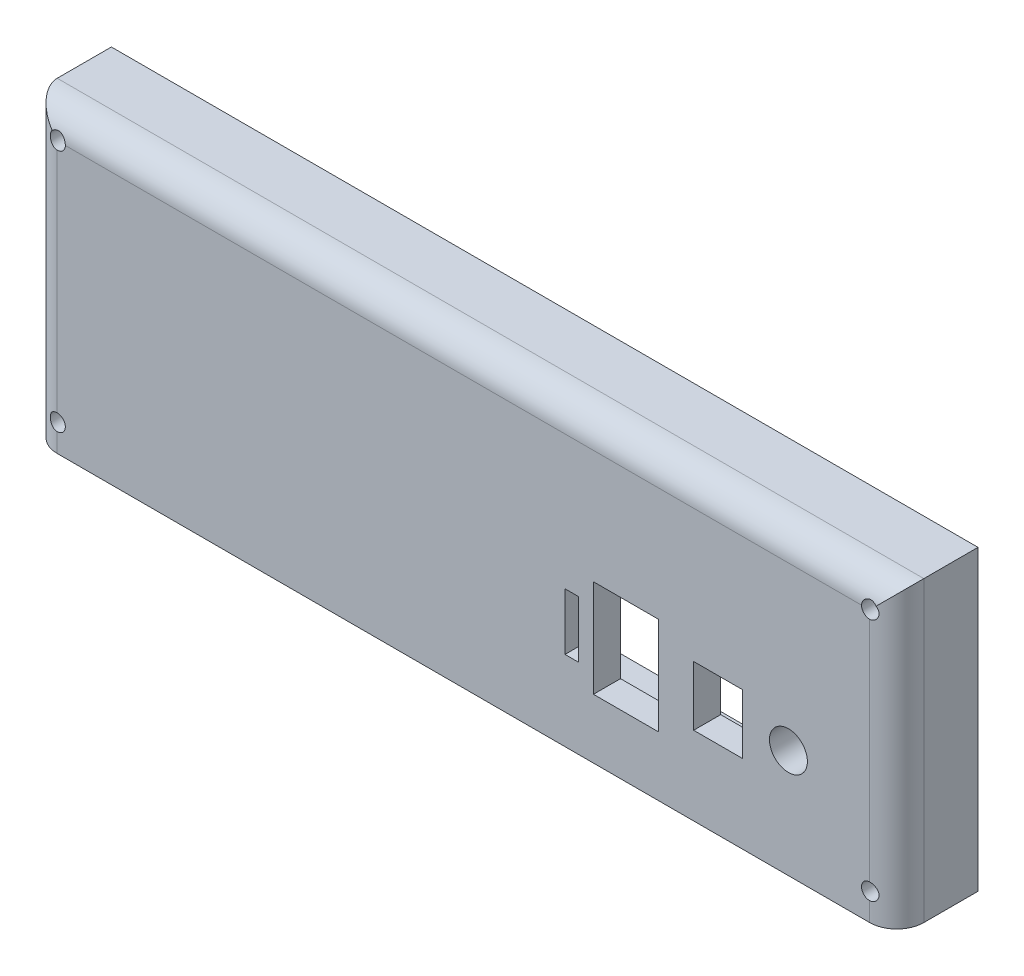
SolidWorks part; units mm, degrees
ref_plane "Спереди" through (0, 0, 0) normal (0, 0, 1) x (1, 0, 0)
ref_plane "Сверху" through (0, 0, 0) normal (0, 1, 0) x (1, 0, 0)
ref_plane "Справа" through (0, 0, 0) normal (1, 0, 0) x (0, 0, -1)
sketch "Эскиз1" plane through (0, 0, 0) normal (0, 0, 1) x (1, 0, 0)
  line L1 (-80, -27.5) -> (80, -27.5)
  line L2 (-80, -27.5) -> (-80, 27.5)
  line L3 (-80, 27.5) -> (80, 27.5)
  line L4 (80, -27.5) -> (80, 27.5)
  line L5 (-80, -27.5) -> (80, 27.5) construction
  line L6 (-80, 27.5) -> (80, -27.5) construction
  point P0 (0, 0)
  dimension "D1" = 55
  dimension "D2" = 160
extrude "Бобышка-Вытянуть1" add sketch "Эскиз1" along normal blind 5 contours L3 L4 L1 L2
sketch "Эскиз2" plane through (0, 0, 5) normal (0, 0, 1) x (1, 0, 0)
  line L0 (-80, -27.5) -> (80, -27.5) construction
  line L1 (42.5, -2) -> (51.5, -2)
  line L2 (42.5, -2) -> (42.5, -13)
  line L3 (42.5, -13) -> (51.5, -13)
  line L4 (51.5, -2) -> (51.5, -13)
  line L5 (42.5, -2) -> (51.5, -13) construction
  line L6 (42.5, -13) -> (51.5, -2) construction
  line L7 (80, -27.5) -> (80, 27.5) construction
  line L9 (24, 1.5) -> (36, 1.5)
  line L10 (24, 1.5) -> (24, -16.5)
  line L11 (24, -16.5) -> (36, -16.5)
  line L12 (36, 1.5) -> (36, -16.5)
  line L13 (24, 1.5) -> (36, -16.5) construction
  line L14 (24, -16.5) -> (36, 1.5) construction
  line L15 (18.75, -2.25) -> (21.25, -2.25)
  line L16 (18.75, -2.25) -> (18.75, -12.75)
  line L17 (18.75, -12.75) -> (21.25, -12.75)
  line L18 (21.25, -2.25) -> (21.25, -12.75)
  line L19 (18.75, -2.25) -> (21.25, -12.75) construction
  line L20 (18.75, -12.75) -> (21.25, -2.25) construction
  circle A0 centre (60, -7.5) radius 3.5
  point P2 (47, -7.5)
  point P12 (30, -7.5)
  point P17 (20, -7.5)
  dimension "D1" = 7
  dimension "D2" = 9
  dimension "D3" = 11
  dimension "D4" = 20
  dimension "D5" = 20
  dimension "D6" = 20
  dimension "D7" = 33
  dimension "D8" = 18
  dimension "D9" = 12
  dimension "D10" = 50
  dimension "D11" = 20
  dimension "D12" = 2.5
  dimension "D13" = 10.5
  dimension "D14" = 60
  dimension "20" = 20
extrude "Вырез-Вытянуть1" cut sketch "Эскиз2" against normal blind 5
sketch "Эскиз3" plane through (0, 0, 5) normal (0, 0, 1) x (1, 0, 0)
  line L0 (-80, -27.5) -> (-80, 27.5) construction
  line L1 (-80, 27.5) -> (80, 27.5) construction
  line L2 (-80, -27.5) -> (80, -27.5) construction
  line L3 (80, -27.5) -> (80, 27.5) construction
  circle A0 centre (-75, 22.5) radius 1.5
  circle A1 centre (-75, -22.5) radius 1.5
  circle A2 centre (75, 22.5) radius 1.5
  circle A3 centre (75, -22.5) radius 1.5
  dimension "D1" = 3
  dimension "D5" = 3
  dimension "D9" = 3
  dimension "D10" = 3
  dimension "D11" = 5
  dimension "D2" = 5
  dimension "D3" = 5
  dimension "D4" = 5
  dimension "D6" = 5
  dimension "D7" = 5
  dimension "D8" = 5
  dimension "D12" = 5
extrude "Вырез-Вытянуть2" cut sketch "Эскиз3" against normal blind 10
fillet "Скругление1" radius 5 3 edges at (-80, 0, 5) (80, 0, 5) (0, 27.5, 5)
sketch "Эскиз5" plane through (0, 0, 0) normal (0, 0, -1) x (-1, 0, 0)
  line L1 (-80, -27.5) -> (80, -27.5)
  line L2 (-80, -27.5) -> (-80, 27.5)
  line L3 (-80, 27.5) -> (80, 27.5)
  line L4 (80, -27.5) -> (80, 27.5)
  line L5 (-80, -27.5) -> (80, 27.5) construction
  line L6 (-80, 27.5) -> (80, -27.5) construction
  point P0 (0, 0)
extrude "Бобышка-Вытянуть2" add sketch "Эскиз5" along normal blind 10
sketch "Эскиз6" plane through (0, 0, -10) normal (0, 0, -1) x (-1, 0, 0)
  line L0 (80, 27.5) -> (-80, 27.5) construction
  line L1 (-75, -22.5) -> (75, -22.5)
  line L2 (-75, -22.5) -> (-75, 22.5)
  line L3 (-75, 22.5) -> (75, 22.5)
  line L4 (75, -22.5) -> (75, 22.5)
  line L5 (-75, -22.5) -> (75, 22.5) construction
  line L6 (-75, 22.5) -> (75, -22.5) construction
  line L7 (80, -27.5) -> (80, 27.5) construction
  point P0 (0, 0)
  dimension "D1" = 5
  dimension "D2" = 5
extrude "Вырез-Вытянуть3" cut sketch "Эскиз6" against normal blind 10
extrude "Вырез-Вытянуть4" cut sketch "Эскиз3<2>" against normal through all
sketch "Эскиз3<2>" plane through (0, 0, 5) normal (0, 0, 1) x (1, 0, 0) same geometry as "Эскиз3"
